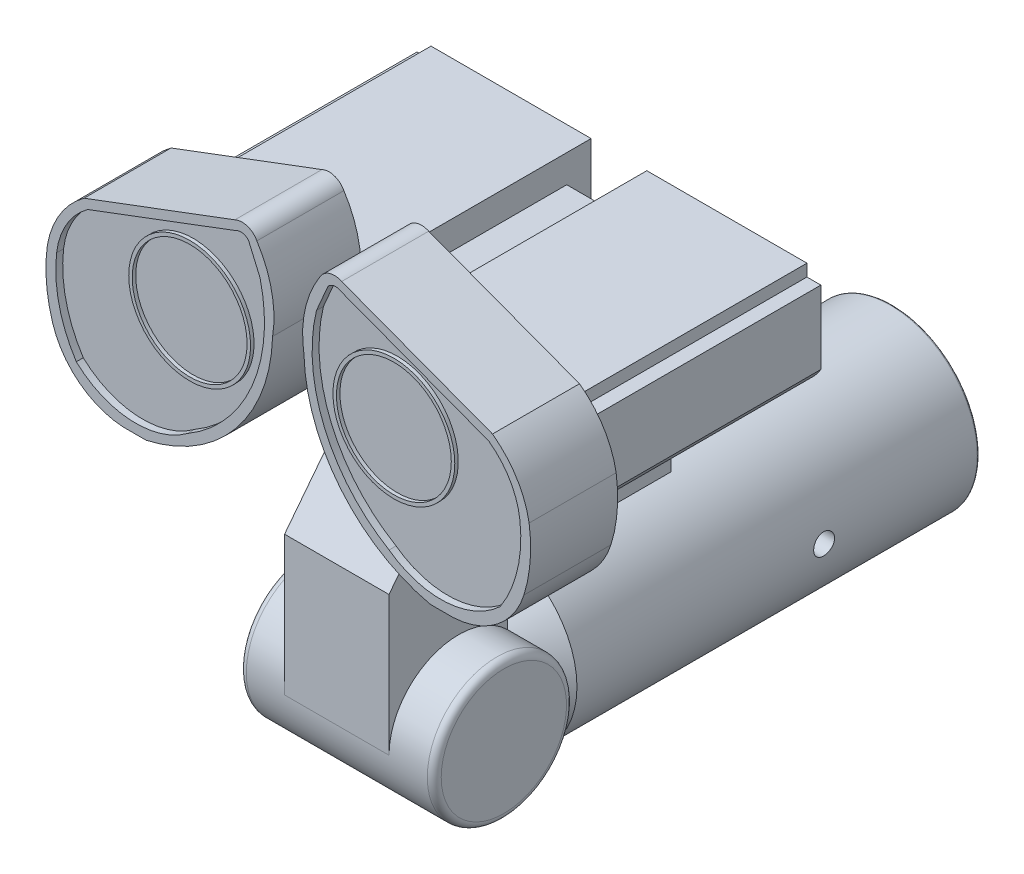
SolidWorks part; units mm, degrees
material "Polyethylene Cross-Linked"
ref_plane "Front" through (0, 0, 0) normal (0, 0, 1) x (1, 0, 0)
ref_plane "Top" through (0, 0, 0) normal (0, 1, 0) x (1, 0, 0)
ref_plane "Right" through (0, 0, 0) normal (1, 0, 0) x (0, 0, -1)
sketch "Sketch2" plane through (0, 0, 0) normal (1, 0, 0) x (0, 0, -1)
  line L0 (0, 1.25) -> (-5.75, 1.25)
  line L3 (3.3, 0) -> (-3.3, 0) construction
  line L4 (-5.75, 1.25) -> (-6.25, 0.75)
  line L5 (-6.25, 0.75) -> (-6.25, 0)
  line L7 (0, 0) -> (0, 1.25)
  line L8 (-6.25, 0) -> (0.1636, 0)
  ellipse E0 centre (0, 0) end of major axis (0, 1.25) minor radius 0.1636 (0.1636, 0) -> (0, 1.25) ccw
  dimension "D1" = 5.75
  dimension "D2" = 1.25
  dimension "D3" = 0.75
  dimension "D4" = 0.5
revolve "Bottom tube" add sketch "Sketch2" angle 360 about L8 region at (0, 0.6175, 3.0769) region at (0, 0.5305, -0.0694)
sketch "Sketch3" plane through (0, 0, 0) normal (1, 0, 0) x (0, 0, -1)
  line L0 (1.375, 0) -> (-1.375, 0) construction
  line L1 (-6.25, 0.75) -> (-6.25, -0.75) construction
  circle A1 centre (-6.95, 0) radius 1
  dimension "D1" = 2
  dimension "D2" = 0.7
extrude "Hinge connected to bottom tube" add sketch "Sketch3" along normal blind 1.4 and the other way blind 1.4
fillet "fillet on hinge" radius 0.1 2 edges at (1.4, 0, 7.95) (-1.4, 0, 7.95)
sketch "Sketch4" plane through (0, 0, 0) normal (1, 0, 0) x (0, 0, -1)
  line L0 (-7.95, 0) -> (-7.95, 2)
  line L1 (-5.75, 1.25) -> (-5.75, -1.25) construction
  line L2 (1.54, 0) -> (-1.54, 0) construction
  line L3 (-6.25, 0.7141) -> (-6.25, 1.5)
  line L4 (-3.8968, 4) -> (-6.3968, 4)
  line L5 (-6.25, 1.5) -> (-3.8968, 1.5)
  line L6 (-3.8968, 1.5) -> (-3.8968, 4)
  line L7 (-6.3968, 4) -> (-7.95, 2)
  line L9 (0, 1.25) -> (-5.75, 1.25) construction
  arc A0 (-6.25, 0.7141) -> (-7.95, 0) centre (-6.95, 0) ccw
  circle A1 centre (-6.95, 0) radius 1 construction
  arc A2 (-6.25, -0.7141) -> (-6.25, 0.7141) centre (-6.95, 0) ccw construction
  dimension "D1" = 0.25
  dimension "D2" = 2
  dimension "D3" = 0.5
  dimension "D4" = 2.5
  dimension "D5" = 2.5
extrude "base connected to eyes" add sketch "Sketch4" along normal blind 0.75 and the other way blind 0.75 contours A0 L0 L7 L4 L6 L5 L3
sketch "Sketch5" plane through (0, 0, 3.8968) normal (0, 0, -1) x (-1, 0, 0)
  line L2 (0, 2.8875) -> (0, -2.8875) construction
  line L7 (2.25, 3.5) -> (-2.25, 3.5)
  line L9 (0.75, 4) -> (-0.75, 4) construction
  line L10 (-2.7, 5.07) -> (-2.7, 4.8972)
  line L11 (-2.7, 4.8972) -> (-2.9, 4.8972)
  line L12 (-2.7, 4.8972) -> (-2.9, 4.8972)
  line L13 (-2.7, 5.07) -> (2.7, 5.07)
  line L14 (2.9, 4.8972) -> (2.9, 3.8472)
  line L15 (-2.9, 4.8972) -> (-2.9, 3.8472)
  line L17 (2.7, 4.8972) -> (2.9, 4.8972)
  line L18 (2.7, 5.07) -> (2.7, 4.8972)
  arc A2 (-2.9, 3.8472) -> (-2.25, 3.5) centre (-2.2926, 4.2023) ccw
  arc A3 (2.9, 3.8472) -> (2.25, 3.5) centre (2.2926, 4.2023) cw
  line M5 (0.75, 4) -> (-0.75, 4)
  line M6 (-0.75, 4) -> (-0.75, 1.5)
  line M8 (0.75, 1.5) -> (0.75, 4)
  dimension "D3" = 0.5
  dimension "D5" = 1.07
  dimension "D7" = 0.2
  dimension "D4" = 5.4
  dimension "D10" = 1.05
  dimension "D11" = 0.2
extrude "Eye backing" add sketch "Sketch5" against normal blind 3.5 contours A3 L14 L17 L18 L13 L10 L11 L15 A2 L7 M6 M5 M8 region at (0, 4.3385, 3.8968)
sketch "Sketch7" plane through (0, 5.07, 0) normal (0, 1, 0) x (1, 0, 0)
  line L0 (2.7, -3.8968) -> (-2.7, -3.8968) construction
  line L1 (-0.4, -3.8968) -> (0.4, -3.8968)
  line L2 (-0.4, -3.8968) -> (-0.4, -7.3968)
  line L3 (-0.4, -7.3968) -> (0.4, -7.3968)
  line L4 (0.4, -3.8968) -> (0.4, -7.3968)
  line L5 (2.7, -7.3968) -> (-2.7, -7.3968) construction
  line L6 (0, -2.8875) -> (0, 2.8875) construction
  dimension "D1" = 0.4
  dimension "D2" = 0.4
extrude "Eye backing details" cut sketch "Sketch7" against normal blind 1.07
sketch "Sketch8" plane through (0, 4, 0) normal (0, 1, 0) x (1, 0, 0)
  line L0 (-0.4, -3.8968) -> (-0.4, -7.3968) construction
  line L1 (-0.4, -4.2468) -> (0.4, -4.2468)
  line L2 (-0.4, -4.2468) -> (-0.4, -6.1468)
  line L3 (-0.4, -6.1468) -> (0.4, -6.1468)
  line L4 (0.4, -4.2468) -> (0.4, -6.1468)
  line L5 (0.4, -7.3968) -> (0.4, -3.8968) construction
  line L7 (0.4, -6.3968) -> (-0.4, -6.3968) construction
  line L8 (0.4, -3.8968) -> (-0.4, -3.8968) construction
  dimension "D1" = 0.25
  dimension "D2" = 0.35
extrude "Middle of eye backing" add sketch "Sketch8" along normal blind 0.67
sketch "Eye sketch" plane through (0, 0, 3.8968) normal (0, 0, -1) x (-1, 0, 0)
  line L0 (0, 4.8457) -> (0, -4.8457) construction
  line L1 (2.3717, 2.871) -> (2.0415, 2.871)
  line L2 (0.7671, 6.2506) -> (2.9333, 5.4363)
  line L10 (50.3928, 177.5032) -> (290.3928, 177.5032) construction
  line L11 (-0.7671, 6.2506) -> (-2.9333, 5.4363)
  line L12 (-2.3717, 2.871) -> (-2.0415, 2.871)
  arc A0 (-2.9333, 5.4363) -> (-3.4597, 4.5924) centre (-2.1493, 4.3611) ccw
  arc A1 (-3.4597, 4.5924) -> (-3.3844, 3.658) centre (-1.3693, 4.2908) ccw
  arc A2 (-3.3844, 3.658) -> (-2.3717, 2.871) centre (-2.296, 4.0134) ccw
  arc A3 (-2.0415, 2.871) -> (-0.2253, 5.07) centre (-2.5477, 5.1386) ccw
  arc A4 (-0.2253, 5.07) -> (-0.451, 6.1456) centre (-1.7381, 5.3141) ccw
  arc A5 (-0.7671, 6.2506) -> (-0.451, 6.1456) centre (-0.6636, 6.0339) cw
  circle A6 centre (-1.4666, 4.7464) radius 0.95
  circle A7 centre (-1.4666, 4.7464) radius 0.375
  arc A8 (0.7671, 6.2506) -> (0.451, 6.1456) centre (0.6636, 6.0339) ccw
  arc A9 (0.2253, 5.07) -> (0.451, 6.1456) centre (1.7381, 5.3141) cw
  arc A10 (2.0415, 2.871) -> (0.2253, 5.07) centre (2.5477, 5.1386) cw
  circle A11 centre (1.4666, 4.7464) radius 0.375
  circle A12 centre (1.4666, 4.7464) radius 0.95
  arc A13 (3.3844, 3.658) -> (2.3717, 2.871) centre (2.296, 4.0134) cw
  arc A14 (3.4597, 4.5924) -> (3.3844, 3.658) centre (1.3693, 4.2908) cw
  arc A15 (2.9333, 5.4363) -> (3.4597, 4.5924) centre (2.1493, 4.3611) cw
  dimension "D1" = 1.9
  dimension "D2" = 0.75
  dimension "D6" = 1.3307
sketch "Sketch12" plane through (0, 0, 7.3968) normal (0, 0, 1) x (1, 0, 0)
  line L0 (-0.7671, 6.2506) -> (-2.9333, 5.4363)
  line L1 (-2.3717, 2.871) -> (-2.0415, 2.871)
  line L2 (0, -3.476) -> (0, 3.476) construction
  line L3 (2.3717, 2.871) -> (2.0415, 2.871)
  line L4 (0.7671, 6.2506) -> (2.9333, 5.4363)
  arc A0 (-2.9333, 5.4363) -> (-3.4597, 4.5924) centre (-2.1493, 4.3611) ccw
  arc A1 (-3.4597, 4.5924) -> (-3.3844, 3.658) centre (-1.3693, 4.2908) ccw
  arc A2 (-3.3844, 3.658) -> (-2.3717, 2.871) centre (-2.31, 3.9954) ccw
  arc A3 (-2.0415, 2.871) -> (-0.2253, 5.07) centre (-2.5477, 5.1386) ccw
  arc A4 (-0.2253, 5.07) -> (-0.451, 6.1456) centre (-1.7381, 5.3141) ccw
  arc A5 (-0.451, 6.1456) -> (-0.7671, 6.2506) centre (-0.6636, 6.0339) ccw
  circle A7 centre (-1.4666, 4.7464) radius 0.875
  arc A8 (2.0415, 2.871) -> (0.2253, 5.07) centre (2.5477, 5.1386) cw
  arc A9 (3.3844, 3.658) -> (2.3717, 2.871) centre (2.31, 3.9954) cw
  arc A11 (0.451, 6.1456) -> (0.7671, 6.2506) centre (0.6636, 6.0339) cw
  arc A12 (0.2253, 5.07) -> (0.451, 6.1456) centre (1.7381, 5.3141) cw
  arc A13 (3.4597, 4.5924) -> (3.3844, 3.658) centre (1.3693, 4.2908) cw
  arc A14 (2.9333, 5.4363) -> (3.4597, 4.5924) centre (2.1493, 4.3611) cw
  circle A15 centre (1.4666, 4.7464) radius 0.875
  circle A16 centre (-1.4666, 4.7464) radius 0.825
  circle A17 centre (1.4666, 4.7464) radius 0.825
  line M1 (-0.75, 4) -> (-0.4, 4)
  line M2 (-0.4, 4) -> (-0.4, 5.07)
  line M3 (-0.4, 5.07) -> (-2.7, 5.07)
  line M4 (-2.7, 5.07) -> (-2.7, 4.8972)
  line M5 (-2.7, 4.8972) -> (-2.9, 4.8972)
  line M6 (-2.9, 4.8972) -> (-2.9, 3.8472)
  arc M7 (-2.9, 3.8472) -> (-2.25, 3.5) centre (-2.2926, 4.2023) ccw
  line M8 (-2.25, 3.5) -> (-0.75, 3.5)
  line M9 (-0.75, 3.5) -> (-0.75, 4)
  dimension "D1" = 1.75
  dimension "D3" = 0.05
extrude "Outer eye" add sketch "Sketch12" along normal blind 1.25 contours A7 A3 A4 A5 L0 A0 A1 A2 L1 M3 M2 M8 M7 M6 M5 M4 | A3 M9 M1 | A7 A3 M3 M4 M5 M6 M7 M8 M9 M1 M2 | A14 L4 A11 A12 A8 L3 A9 A13 A15 region at (-0.6028, 6.217, 7.3968) region at (-0.484, 4.1372, 7.3968) region at (-0.6717, 3.8855, 7.3968) region at (2.2066, 2.9183, 7.3968)
sketch "Sketch13" plane through (0, 0, 8.6468) normal (0, 0, 1) x (1, 0, 0)
  line L0 (-0.758, 6.1213) -> (-2.8802, 5.3222)
  line L1 (-0.5701, 6.0916) -> (-0.4049, 5.7086)
  line L2 (0, -3.476) -> (0, 3.476) construction
  line L3 (0.5701, 6.0916) -> (0.4049, 5.7086)
  line L4 (0.758, 6.1213) -> (2.8802, 5.3222)
  arc A0 (-2.8802, 5.3222) -> (-3.3276, 4.5598) centre (-2.2369, 4.4322) ccw
  arc A1 (-3.3276, 4.5598) -> (-3.0448, 3.3456) centre (-1.4983, 4.3458) ccw
  arc A2 (-3.0448, 3.3456) -> (-1.4485, 3.2519) centre (-2.1905, 4.2551) ccw
  arc A3 (-1.4485, 3.2519) -> (-0.4049, 5.7086) centre (-2.5792, 5.1822) ccw
  arc A5 (-0.758, 6.1213) -> (-0.5701, 6.0916) centre (-0.6809, 5.9995) cw
  arc A6 (1.4485, 3.2519) -> (0.4049, 5.7086) centre (2.5792, 5.1822) cw
  arc A7 (0.758, 6.1213) -> (0.5701, 6.0916) centre (0.6809, 5.9995) ccw
  arc A8 (3.0448, 3.3456) -> (1.4485, 3.2519) centre (2.1905, 4.2551) cw
  arc A9 (3.3276, 4.5598) -> (3.0448, 3.3456) centre (1.4983, 4.3458) cw
  arc A10 (2.8802, 5.3222) -> (3.3276, 4.5598) centre (2.2369, 4.4322) cw
extrude "Inner eye cut" cut sketch "Sketch13" against normal blind 0.1
extrude "Outer lens" add sketch "Sketch12<5>" along normal blind 1.2 contours A16 A7 M3 | A16 A7 M3 | A15 A17 region at (-1.6274, 3.9079, 7.3968) region at (-0.6807, 5.0872, 7.3968) region at (0.6164, 4.7464, 7.3968)
sketch "Sketch12<5>" plane through (0, 0, 7.3968) normal (0, 0, 1) x (1, 0, 0) same geometry as "Sketch12"
extrude "Inner lens cut" add sketch "Sketch12<7>" along normal blind 1.15 contours A16 M3 | A16 M3 | A17 region at (-1.4666, 5.2769, 7.3968) region at (-1.4666, 4.563, 7.3968) region at (1.4666, 4.7464, 7.3968)
sketch "Sketch12<7>" plane through (0, 0, 7.3968) normal (0, 0, 1) x (1, 0, 0) same geometry as "Sketch12"
sketch "Sketch15" plane through (0, 0, 0) normal (1, 0, 0) x (0, 0, -1)
  line L0 (3.8295, 0) -> (-3.8295, 0) construction
  line L1 (0, 3.8295) -> (0, -3.8295) construction
  circle A0 centre (-2.2, 0) radius 0.15
  dimension "D1" = 0.3
  dimension "D2" = 2.2
extrude "Cut-Extrude3" cut sketch "Sketch15" against normal up to next and the other way up to next
extrude "Boss-Extrude16" add sketch "Sketch12<6>" along normal blind 1.15 contours A16 M3 | A16 M3 | A17 region at (-1.4666, 5.2769, 7.3968) region at (-1.4666, 4.563, 7.3968) region at (1.4666, 4.7464, 7.3968)
sketch "Sketch12<6>" plane through (0, 0, 7.3968) normal (0, 0, 1) x (1, 0, 0) same geometry as "Sketch12"
equation "\"D2@Sketch7\"=\"D1@Sketch7\""
